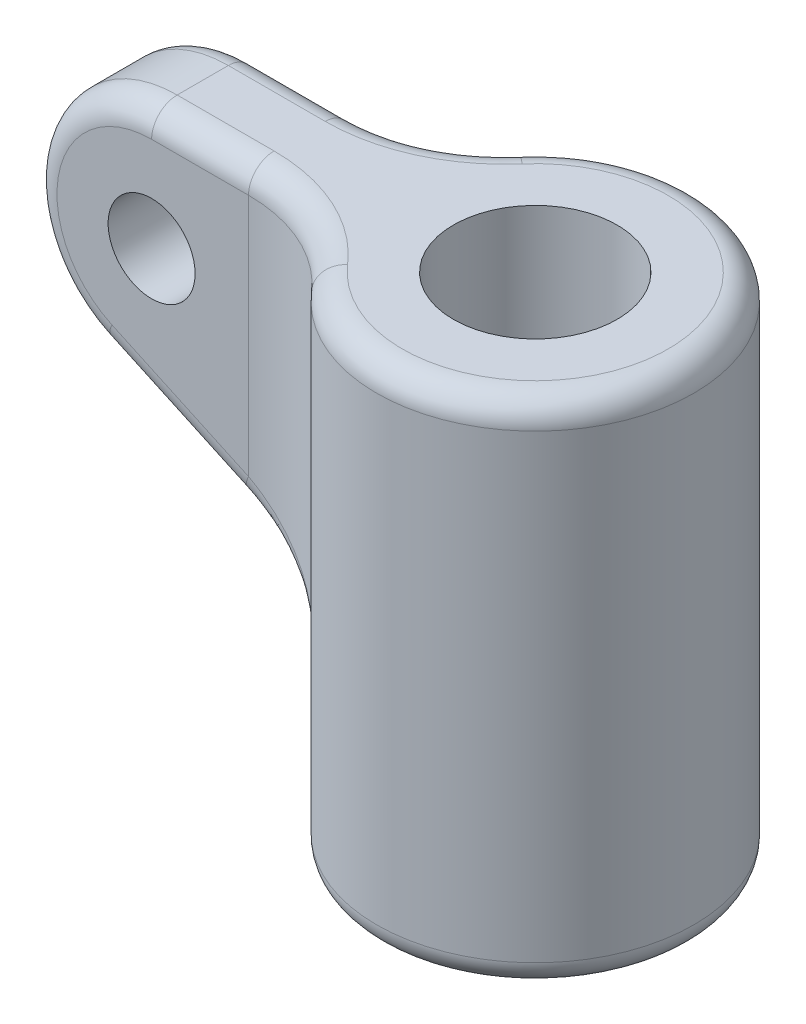
SolidWorks part; units mm, degrees
ref_plane "Front Plane" through (0, 0, 0) normal (0, 0, 1) x (1, 0, 0)
ref_plane "Top Plane" through (0, 0, 0) normal (0, 1, 0) x (1, 0, 0)
ref_plane "Right Plane" through (0, 0, 0) normal (1, 0, 0) x (0, 0, -1)
sketch "Sketch2" plane through (0, 0, 0) normal (0, 1, 0) x (1, 0, 0)
  circle A0 centre (0, 0) radius 3.2
  circle A1 centre (0, 0) radius 6.2
  dimension "D1" = 6.4
  dimension "D2" = 3
extrude "Boss-Extrude1" add sketch "Sketch2" along normal blind 20 contours A1 A0 region at (-6.0246, 0, 0)
sketch "Sketch3" plane through (0, 0, 0) normal (0, 0, 1) x (1, 0, 0)
  line L0 (-6.2, 20) -> (-13, 20)
  line L2 (-14.9697, 11.0327) -> (-5.0786, 6.467)
  line L4 (-6.2, 20) -> (0, 20)
  line L5 (0, 20) -> (0, 6.467)
  line L6 (0, 6.467) -> (-5.0786, 6.467)
  arc A0 (-13, 20) -> (-14.9697, 11.0327) centre (-13, 15.3) ccw
  circle A1 centre (-13, 15.3) radius 1.7
  point P6 (-5.3243, 4.3775)
  point P7 (-5.6651, 4.5053)
  point P10 (-6.2, 4.3349)
  point P11 (-5.0786, 6.467)
  dimension "D1" = 3.4
  dimension "D2" = 3
  dimension "D3" = 13
extrude "Boss-Extrude2" add sketch "Sketch3" along normal blind 2 and the other way blind 2
fillet "Fillet1" radius 6 2 edges at (-5.8686, 13.4158, 2) (-5.8686, 13.4158, -2)
extrude "Cut-Extrude1" cut sketch "Sketch2<3>" along normal up to surface (20 mm away) contours A0 region at (0, 0, 0) up to face at (0.1755, 20, 0)
sketch "Sketch2<3>" plane through (0, 0, 0) normal (0, 1, 0) x (1, 0, 0) same geometry as "Sketch2"
fillet "Fillet3" radius 1 1 edges at (0, 0, 6.2)
fillet "Fillet4" radius 1 11 edges at (-6.7215, 7.2254, 2.5408) (-12.0903, 9.7036, 2) (-17.5906, 16.3084, 2) (-11.1054, 20, 2) (-6.7215, 20, 2.5408) (-6.7215, 7.2254, -2.5408) (-12.0903, 9.7036, -2) (-17.5906, 16.3084, -2) (-11.1054, 20, -2) (-6.7215, 20, -2.5408) (6.2, 20, 0)
